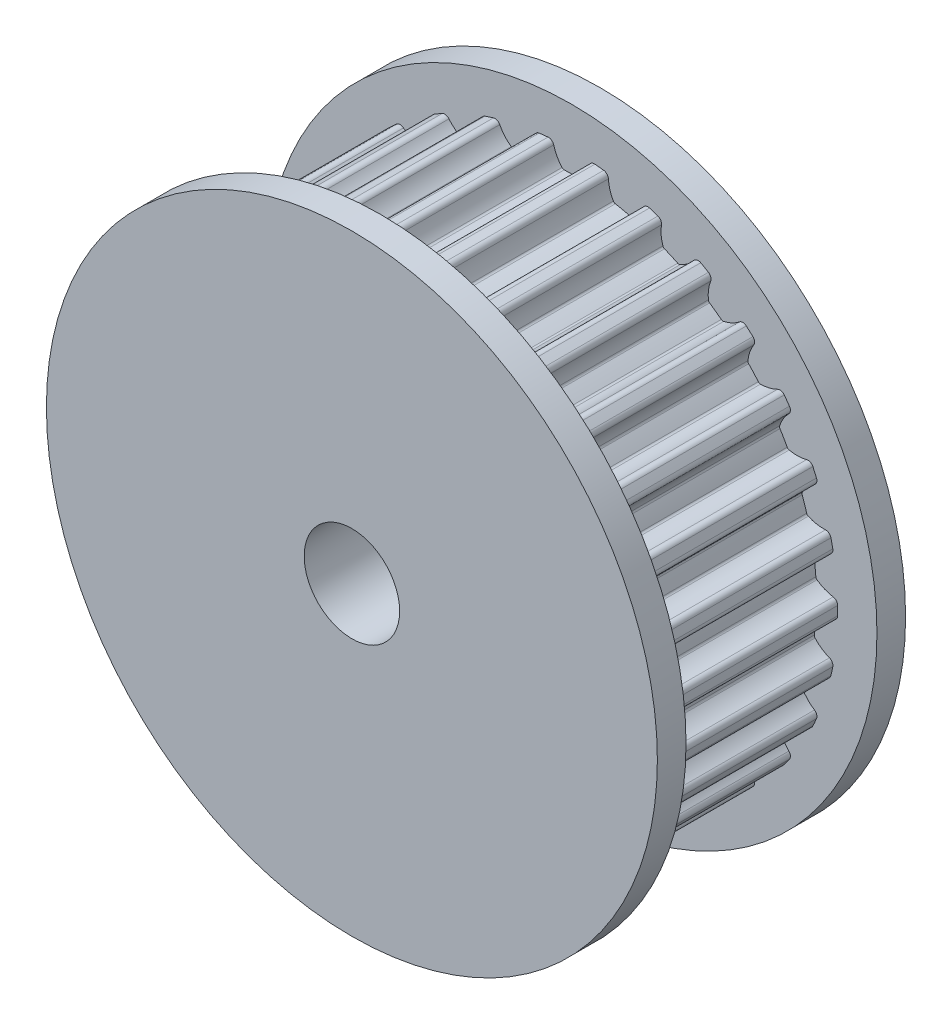
SolidWorks part; units mm, degrees
material "6061-T6 (SS)"
ref_plane "前基準面" through (0, 0, 0) normal (0, 0, 1) x (1, 0, 0)
ref_plane "上基準面" through (0, 0, 0) normal (0, 1, 0) x (1, 0, 0)
ref_plane "右基準面" through (0, 0, 0) normal (1, 0, 0) x (0, 0, -1)
sketch "草圖1" plane through (0, 0, 0) normal (0, 0, 1) x (1, 0, 0)
  circle A0 centre (0, 0) radius 13.945
  dimension "D1" = 27.89
extrude "填料-伸長1" add sketch "草圖1" along normal mid plane 10
sketch "草圖2" plane through (0, 0, 5) normal (0, 0, 1) x (1, 0, 0)
  line L0 (0, 0) -> (0, 13.945) construction
  line L1 (0, 13.945) -> (0, 14.199) construction
  line L2 (-0.975, 14.199) -> (0.975, 14.199) construction
  circle A0 centre (0, 0) radius 13.945 construction
  arc A1 (-0.3782, 12.8294) -> (0.3782, 12.8294) centre (0, 0) cw
  arc A2 (-0.3782, 12.8294) -> (-0.4942, 12.8791) centre (-0.3826, 12.9794) cw
  arc A3 (-0.4942, 12.8791) -> (-0.9319, 13.6849) centre (0.975, 14.199) cw
  arc A4 (-1.2269, 13.8909) -> (-0.9319, 13.6849) centre (-1.2023, 13.612) cw
  arc A5 (0.3782, 12.8294) -> (0.4942, 12.8791) centre (0.3826, 12.9794) ccw
  arc A6 (0.4942, 12.8791) -> (0.9319, 13.6849) centre (-0.975, 14.199) ccw
  arc A7 (1.2269, 13.8909) -> (0.9319, 13.6849) centre (1.2023, 13.612) ccw
  arc A8 (-1.2269, 13.8909) -> (1.2269, 13.8909) centre (0, 0) cw
  dimension "D1" = 0.15
  dimension "D2" = 1.975
  dimension "D3" = 0.28
  dimension "D4" = 1.11
  dimension "D5" = 0.254
  dimension "D6" = 1.95
extrude "除料-伸長1" cut sketch "草圖2" against normal through all and the other way through all
pattern_circular "環狀複製排列1" count 30 over 360 about axis through (0, 0, 5) along (0, 0, -1) of "除料-伸長1" reverse direction yes
sketch "草圖3" plane through (0, 0, 5) normal (0, 0, 1) x (1, 0, 0)
  circle A0 centre (0, 0) radius 16
  dimension "D1" = 32
extrude "填料-伸長2" add sketch "草圖3" along normal blind 1.5
sketch "草圖9" plane through (0, 0, -5) normal (0, 0, -1) x (-1, 0, 0)
  circle A0 centre (0, 0) radius 16
  circle A1 centre (0, 0) radius 16 construction
extrude "填料-伸長3" add sketch "草圖9" along normal blind 1.5
sketch "草圖4" plane through (0, 0, 6.5) normal (0, 0, 1) x (1, 0, 0)
  circle A0 centre (0, 0) radius 2.5
  dimension "D1" = 5
extrude "除料-伸長2" cut sketch "草圖4" against normal through all and the other way blind 8
sketch "草圖10" plane through (0, 0, 0) normal (0, 1, 0) x (1, 0, 0)
  circle A0 centre (0, 0) radius 2
  dimension "D1" = 4
extrude "除料-伸長3" cut sketch "草圖10" against normal through all
sketch "草圖11" plane through (0, 0, 0) normal (1, 0, 0) x (0, 0, -1)
  circle A0 centre (0, 0) radius 2
  dimension "D1" = 4
extrude "除料-伸長4" cut sketch "草圖11" against normal through all
